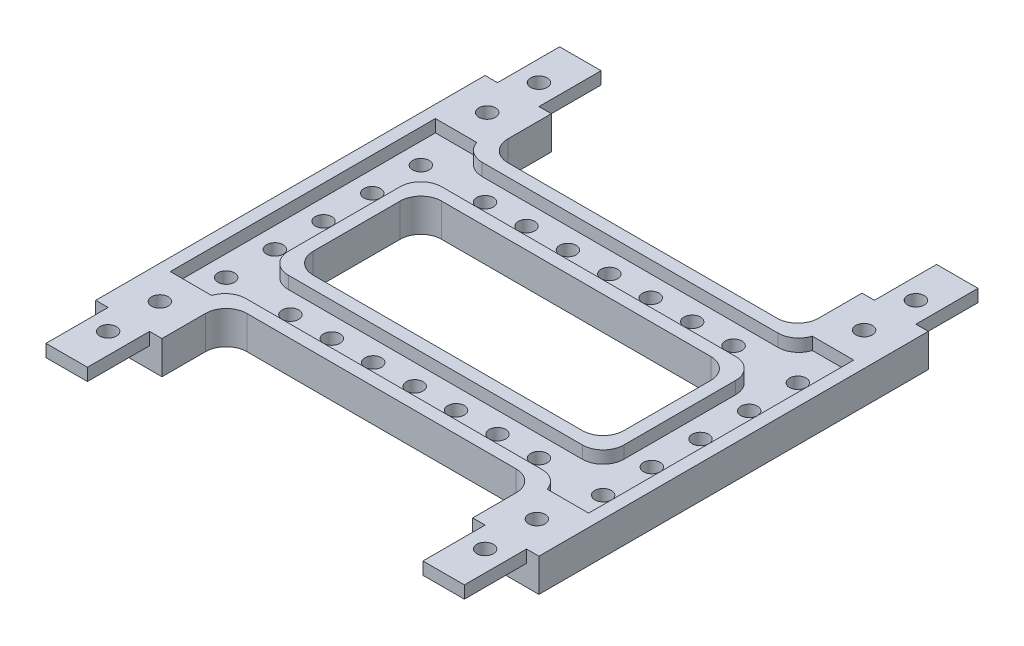
SolidWorks part; units mm, degrees
ref_plane "Front Plane" through (0, 0, 0) normal (0, 0, 1) x (1, 0, 0)
ref_plane "Top Plane" through (0, 0, 0) normal (0, 1, 0) x (1, 0, 0)
ref_plane "Right Plane" through (0, 0, 0) normal (1, 0, 0) x (0, 0, -1)
sketch "Sketch1" plane through (0, 0, 0) normal (0, 1, 0) x (1, 0, 0)
  line L7 (-51.0658, -44.1786) -> (-59.0658, -44.1786)
  line L9 (-59.0658, -44.1786) -> (-59.0658, 49.8214)
  line L10 (39.9342, -44.1786) -> (47.9342, -44.1786)
  line L14 (47.9342, -44.1786) -> (47.9342, 49.8214)
  line L18 (47.9342, 49.8214) -> (39.9342, 49.8214)
  line L19 (-59.0658, 49.8214) -> (-51.0658, 49.8214)
  line L20 (-51.0658, 49.8214) -> (-43.0658, 49.8214)
  line L22 (-43.0658, -44.1786) -> (-51.0658, -44.1786)
  line L23 (39.9342, 49.8214) -> (31.9342, 49.8214)
  line L25 (31.9342, -44.1786) -> (39.9342, -44.1786)
  line L26 (-43.0658, 49.8214) -> (-43.0658, 39.3214)
  line L29 (-43.0658, 13.3214) -> (-43.0658, -7.6786)
  line L30 (26.9342, -12.6786) -> (-38.0658, -12.6786)
  line L32 (26.9342, -28.6786) -> (-38.0658, -28.6786)
  line L34 (-43.0658, -33.6786) -> (-43.0658, -44.1786)
  line L35 (-38.0658, 34.3214) -> (26.9342, 34.3214)
  line L36 (31.9342, -33.6786) -> (31.9342, -44.1786)
  line L37 (-38.0658, 18.3214) -> (26.9342, 18.3214)
  line L38 (31.9342, -7.6786) -> (31.9342, 13.3214)
  line L39 (31.9342, 39.3214) -> (31.9342, 49.8214)
  line L40 (-43.0658, 39.3214) -> (-43.0658, 34.3214)
  line L41 (-43.0658, 34.3214) -> (-38.0658, 34.3214)
  line L42 (-43.0658, 13.3214) -> (-43.0658, 18.3214)
  line L43 (-43.0658, 18.3214) -> (-38.0658, 18.3214)
  line L44 (26.9342, 34.3214) -> (31.9342, 34.3214)
  line L45 (31.9342, 39.3214) -> (31.9342, 34.3214)
  line L46 (26.9342, 18.3214) -> (31.9342, 18.3214)
  line L47 (31.9342, 18.3214) -> (31.9342, 13.3214)
  line L48 (31.9342, -7.6786) -> (31.9342, -12.6786)
  line L49 (31.9342, -12.6786) -> (26.9342, -12.6786)
  line L50 (26.9342, -28.6786) -> (31.9342, -28.6786)
  line L51 (31.9342, -28.6786) -> (31.9342, -33.6786)
  line L52 (-38.0658, -28.6786) -> (-43.0658, -28.6786)
  line L53 (-43.0658, -28.6786) -> (-43.0658, -33.6786)
  line L54 (-43.0658, -7.6786) -> (-43.0658, -12.6786)
  line L55 (-43.0658, -12.6786) -> (-38.0658, -12.6786)
extrude "Boss-Extrude2" add sketch "Sketch1" along normal blind 5
sketch "Sketch3" plane through (0, 5, 0) normal (0, 1, 0) x (1, 0, 0)
  line L0 (-59.0658, 49.8214) -> (-56.0658, 49.8214)
  line L1 (-43.0658, 49.8214) -> (-59.0658, 49.8214) construction
  line L2 (-56.0658, 49.8214) -> (-56.0658, -44.1786)
  line L3 (-59.0658, -44.1786) -> (-43.0658, -44.1786) construction
  line L4 (-56.0658, -44.1786) -> (-59.0658, -44.1786)
  line L5 (-59.0658, -44.1786) -> (-59.0658, 49.8214)
  line L6 (47.9342, 49.8214) -> (44.9342, 49.8214)
  line L7 (47.9342, 49.8214) -> (31.9342, 49.8214) construction
  line L8 (44.9342, 49.8214) -> (44.9342, -44.1786)
  line L9 (31.9342, -44.1786) -> (47.9342, -44.1786) construction
  line L10 (44.9342, -44.1786) -> (47.9342, -44.1786)
  line L11 (47.9342, -44.1786) -> (47.9342, 49.8214)
  line L12 (-43.0658, 49.8214) -> (-46.0658, 49.8214)
  line L14 (-46.0658, 49.8214) -> (-46.0658, 34.3214)
  line L15 (-46.0658, 34.3214) -> (-46.0658, 31.3214)
  line L16 (-46.0658, 31.3214) -> (31.9342, 31.3214)
  line L18 (31.9342, 31.3214) -> (34.9342, 31.3214)
  line L19 (34.9342, 31.3214) -> (34.9342, 49.8214)
  line L20 (34.9342, 49.8214) -> (31.9342, 49.8214)
  line L21 (31.9342, 49.8214) -> (31.9342, 34.3214)
  line L22 (-43.0658, 34.3214) -> (-43.0658, 49.8214)
  line L23 (31.9342, 34.3214) -> (-43.0658, 34.3214)
  line L24 (34.9342, 21.3214) -> (34.9342, -12.6786)
  line L25 (31.9342, 21.3214) -> (34.9342, 21.3214)
  line L28 (34.9342, -12.6786) -> (34.9342, -15.6786)
  line L29 (34.9342, -15.6786) -> (-46.0658, -15.6786)
  line L30 (-46.0658, -15.6786) -> (-46.0658, 21.3214)
  line L31 (-46.0658, 21.3214) -> (31.9342, 21.3214)
  line L32 (-46.0658, -44.1786) -> (-43.0658, -44.1786)
  line L33 (-43.0658, -44.1786) -> (-43.0658, -28.6786)
  line L34 (-43.0658, -28.6786) -> (31.9342, -28.6786)
  line L35 (31.9342, -28.6786) -> (31.9342, -44.1786)
  line L36 (31.9342, -44.1786) -> (34.9342, -44.1786)
  line L38 (34.9342, -28.6786) -> (34.9342, -25.6786)
  line L39 (34.9342, -25.6786) -> (-46.0658, -25.6786)
  line L40 (-46.0658, -25.6786) -> (-46.0658, -44.1786)
  line L41 (34.9342, -28.6786) -> (34.9342, -44.1786)
  line L42 (-43.0658, 18.3214) -> (31.9342, 18.3214)
  line L43 (31.9342, 18.3214) -> (31.9342, -12.6786)
  line L44 (31.9342, -12.6786) -> (-43.0658, -12.6786)
  line L45 (-43.0658, -12.6786) -> (-43.0658, 18.3214)
extrude "Boss-Extrude4" add sketch "Sketch3" along normal blind 3
sketch "Sketch4" plane through (0, 5, 0) normal (0, 1, 0) x (1, 0, 0)
  line L0 (-46.0658, -59.1786) -> (-46.0658, -29.1786)
  line L3 (39.9342, -59.1786) -> (44.9342, -59.1786)
  line L4 (44.9342, -59.1786) -> (44.9342, -29.1786)
  line L5 (44.9342, 49.8214) -> (44.9342, -44.1786) construction
  line L6 (44.9342, -29.1786) -> (34.9342, -29.1786)
  line L7 (34.9342, -44.1786) -> (34.9342, -25.6786) construction
  line L8 (34.9342, -29.1786) -> (34.9342, -59.1786)
  line L9 (34.9342, -59.1786) -> (39.9342, -59.1786)
  line L10 (-46.0658, -29.1786) -> (-56.0658, -29.1786)
  line L11 (-56.0658, -29.1786) -> (-56.0658, -59.1786)
  line L12 (-56.0658, -59.1786) -> (-51.0658, -59.1786)
  line L13 (-51.0658, -59.1786) -> (-46.0658, -59.1786)
  line L14 (-46.0658, 34.8214) -> (-46.0658, 64.8214)
  line L15 (-46.0658, 64.8214) -> (-56.0658, 64.8214)
  line L16 (-56.0658, 64.8214) -> (-56.0658, 34.8214)
  line L17 (-56.0658, 34.8214) -> (-51.0658, 34.8214)
  line L18 (-51.0658, 34.8214) -> (-46.0658, 34.8214)
  line L19 (44.9342, 34.8214) -> (44.9342, 64.8214)
  line L20 (44.9342, 64.8214) -> (34.9342, 64.8214)
  line L21 (34.9342, 64.8214) -> (34.9342, 34.8214)
  line L22 (34.9342, 34.8214) -> (39.9342, 34.8214)
  line L23 (39.9342, 34.8214) -> (44.9342, 34.8214)
extrude "Boss-Extrude5" add sketch "Sketch4" along normal blind 3
sketch "Sketch5" plane through (0, 5, 0) normal (0, 1, 0) x (1, 0, 0)
  circle A0 centre (-51.0658, 26.3214) radius 2
  circle A1 centre (39.9342, 26.3214) radius 2
  circle A2 centre (39.9342, -20.6786) radius 2
  circle A3 centre (-51.0658, -20.6786) radius 2
  circle A4 centre (-51.0658, 2.8214) radius 2
  circle A5 centre (39.9342, 2.8214) radius 2
  circle A6 centre (-51.0658, 14.5714) radius 2
  circle A7 centre (-51.0658, -8.9286) radius 2
  circle A17 centre (-5.5658, 26.3214) radius 2
  circle A18 centre (14.4342, 26.3214) radius 2
  circle A19 centre (24.4342, 26.3214) radius 2
  circle A20 centre (-25.5658, 26.3214) radius 2
  circle A21 centre (4.4342, 26.3214) radius 2
  circle A22 centre (-35.5658, 26.3214) radius 2
  circle A23 centre (-15.5658, 26.3214) radius 2
  circle A24 centre (-5.5658, -20.6786) radius 2
  circle A25 centre (14.4342, -20.6786) radius 2
  circle A26 centre (24.4342, -20.6786) radius 2
  circle A27 centre (-25.5658, -20.6786) radius 2
  circle A28 centre (4.4342, -20.6786) radius 2
  circle A29 centre (-35.5658, -20.6786) radius 2
  circle A30 centre (-15.5658, -20.6786) radius 2
  circle A31 centre (39.9342, 14.5714) radius 2
  circle A32 centre (39.9342, -8.9286) radius 2
extrude "Cut-Extrude1" cut sketch "Sketch5" against normal up to surface (5 mm away) up to face at (-5.5658, 0, -2.8214)
sketch "Sketch6" plane through (0, 5, 0) normal (0, -1, 0) x (1, 0, 0)
  circle A0 centre (39.9342, -54.8214) radius 2
  circle A1 centre (-51.0658, -54.8214) radius 2
  circle A2 centre (-51.0658, 49.1786) radius 2
  circle A3 centre (39.9342, 49.1786) radius 2
extrude "Cut-Extrude2" cut sketch "Sketch6" against normal up to surface (3 mm away) up to face at (-5.5658, 8, -2.8214)
sketch "Sketch7" plane through (0, 8, 0) normal (0, 1, 0) x (1, 0, 0)
  circle A0 centre (-51.0658, 42.3214) radius 2
  circle A1 centre (39.9342, 42.3214) radius 2
  circle A2 centre (-51.0658, -36.6786) radius 2
  circle A3 centre (39.9342, -36.6786) radius 2
extrude "Cut-Extrude3" cut sketch "Sketch7" against normal up to surface (8 mm away) up to face at (39.9342, 0, -12.5714)
fillet "Fillet1" radius 5 8 edges at (-43.0658, 4, -34.3214) (31.9342, 4, -34.3214) (31.9342, 4, 28.6786) (-43.0658, 4, 28.6786) (31.9342, 4, 12.6786) (31.9342, 4, -18.3214) (-43.0658, 4, -18.3214) (-43.0658, 4, 12.6786)
fillet "Fillet2" radius 5 8 edges at (-46.0658, 6.5, 25.6786) (-46.0658, 6.5, 15.6786) (-46.0658, 6.5, -21.3214) (-46.0658, 6.5, -31.3214) (34.9342, 6.5, 25.6786) (34.9342, 6.5, 15.6786) (34.9342, 6.5, -21.3214) (34.9342, 6.5, -31.3214)
